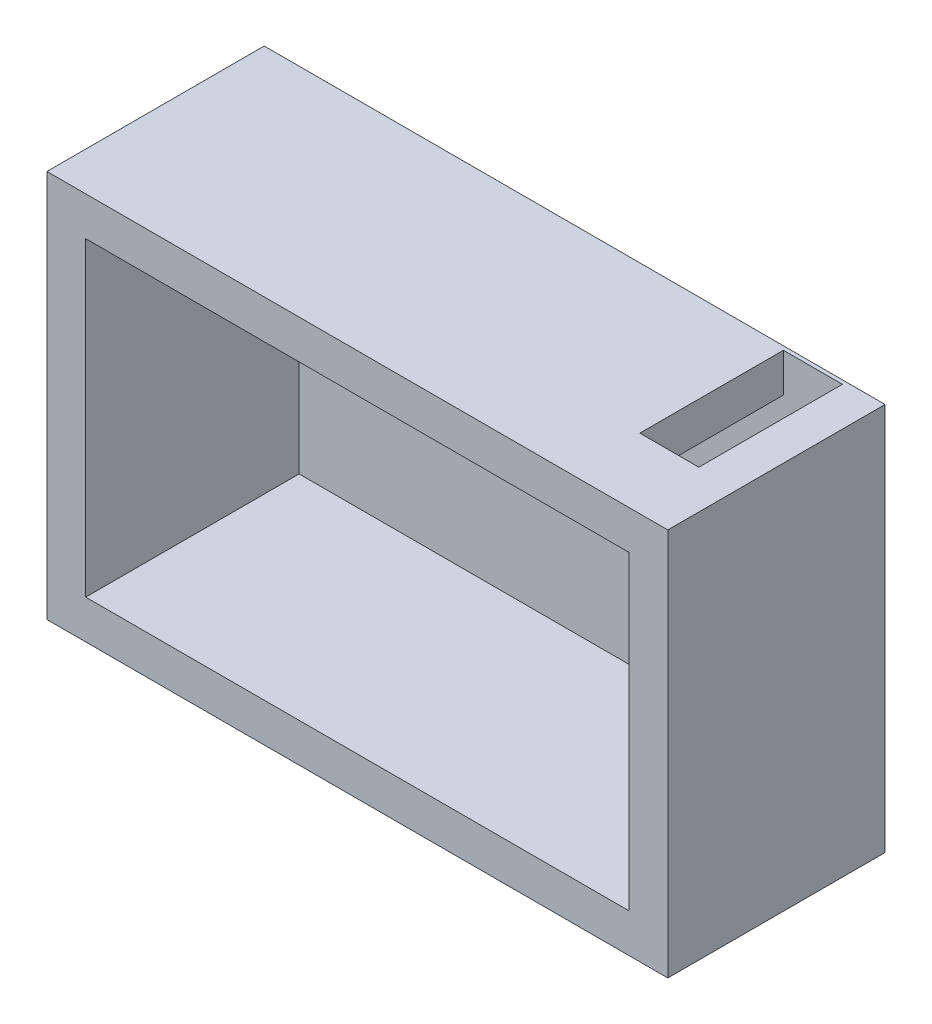
SolidWorks part; units mm, degrees
ref_plane "Front Plane" through (0, 0, 0) normal (0, 0, 1) x (1, 0, 0)
ref_plane "Top Plane" through (0, 0, 0) normal (0, 1, 0) x (1, 0, 0)
ref_plane "Right Plane" through (0, 0, 0) normal (1, 0, 0) x (0, 0, -1)
sketch "Sketch1" plane through (0, 0, 0) normal (0, 0, 1) x (1, 0, 0)
  line L1 (0, 0) -> (8, 0)
  line L2 (0, 0) -> (0, 0.5)
  line L3 (0, 0.5) -> (8, 0.5)
  line L4 (8, 0) -> (8, 0.5)
  line L5 (0, 0) -> (0.5, 0)
  line L6 (0, 0) -> (0, 5)
  line L7 (0, 5) -> (0.5, 5)
  line L8 (0.5, 0) -> (0.5, 5)
  line L9 (0, 5) -> (6.74, 5)
  line L10 (0, 5) -> (0, 4.5)
  line L11 (0, 4.5) -> (6.74, 4.5)
  line L12 (6.74, 5) -> (6.74, 4.5)
  line L13 (8, 0) -> (7.5, 0)
  line L14 (8, 0) -> (7.5, 0)
  line L15 (8, 0) -> (8, 5)
  line L16 (8, 5) -> (7.5, 5)
  line L17 (0, 5) -> (0.5, 5)
  line L18 (7.5, 0) -> (7.5, 5)
  dimension "D1" = 8
  dimension "D2" = 0.5
  dimension "D3" = 5
  dimension "D4" = 0.5
  dimension "D5" = 0.5
  dimension "D6" = 6.74
  dimension "D7" = 0.5
extrude "Boss-Extrude1" add sketch "Sketch1" along normal blind 2.8 contours L7 | L18 | L16 L18 | L12 L9 L8 L11 | L6 L11 L8 L7 | L18 L3 | L18 L1 L4 L3 | L11 L6 L3 L8 | L1 L8 L3 L2 | L1 L18 L3 L8 region at (0.25, 0.25, 0) region at (4, 0.25, 0) region at (0.25, 2.5, 0) region at (7.75, 0.25, 0) region at (0.25, 4.75, 0) region at (7.75, 2.75, 0) region at (3.62, 4.75, 0)
sketch "Sketch3" plane through (6.74, 0, 0) normal (1, 0, 0) x (0, 0, -1)
  line L0 (-2.8, 5) -> (0, 5) construction
  line L1 (-2.8, 4.5) -> (-1.9, 4.5)
  line L2 (-2.8, 4.5) -> (-2.8, 5)
  line L3 (-2.8, 5) -> (-1.9, 5)
  line L4 (-1.9, 4.5) -> (-1.9, 5)
  line L5 (0, 5) -> (0, 4.5) construction
  dimension "D1" = 1.9
extrude "Boss-Extrude3" add sketch "Sketch3" along normal up to next
sketch "Sketch5" plane through (0.5, 0, 0) normal (1, 0, 0) x (0, 0, -1)
  line L1 (0, 0.5) -> (-0.05, 0.5)
  line L2 (0, 0.5) -> (0, 5)
  line L3 (0, 5) -> (-0.05, 5)
  line L4 (-0.05, 0.5) -> (-0.05, 5)
  point P5 (0, 0)
  dimension "D1" = 0.05
extrude "Boss-Extrude5" add sketch "Sketch5" along normal up to next
